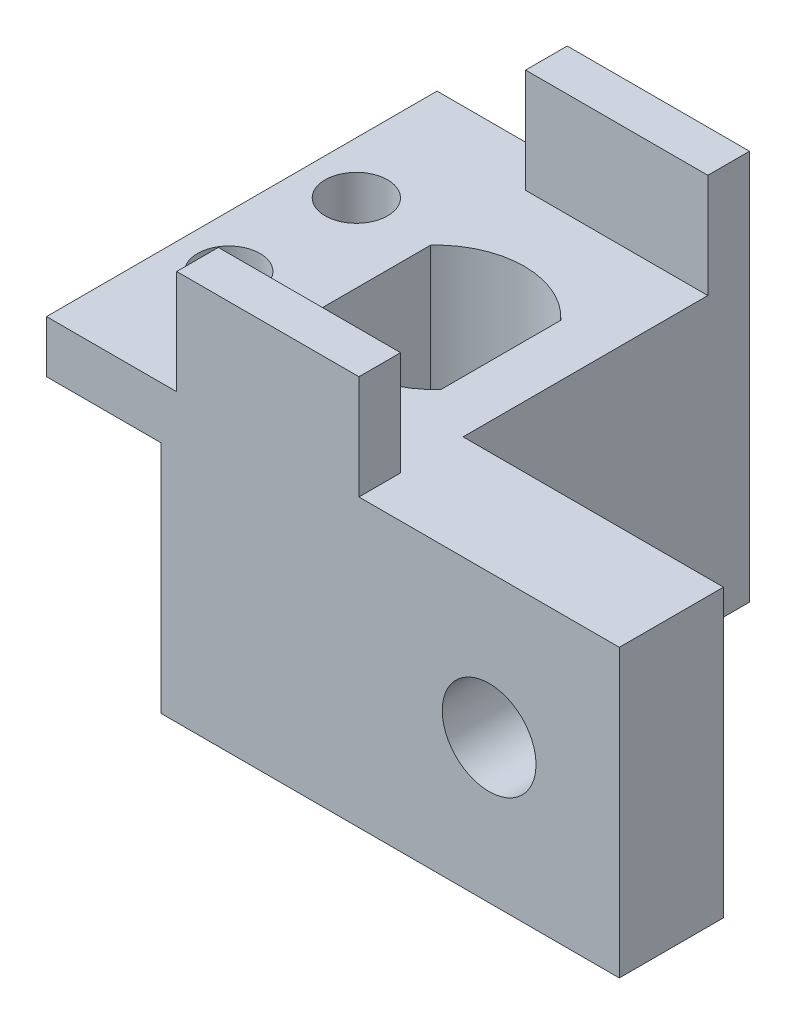
SolidWorks part; units mm, degrees
ref_plane "Front Plane" through (0, 0, 0) normal (0, 0, 1) x (1, 0, 0)
ref_plane "Top Plane" through (0, 0, 0) normal (0, 1, 0) x (1, 0, 0)
ref_plane "Right Plane" through (0, 0, 0) normal (1, 0, 0) x (0, 0, -1)
sketch "Sketch1" plane through (0, 0, 0) normal (0, 1, 0) x (1, 0, 0)
  line L0 (0, 0) -> (12.7, 0)
  line L1 (12.7, 0) -> (12.7, -5.08)
  line L2 (12.7, -5.08) -> (-15.24, -5.08)
  line L3 (-15.24, -5.08) -> (-15.24, 13.97)
  line L4 (-15.24, 13.97) -> (0, 13.97)
  line L5 (0, 13.97) -> (0, 0)
  dimension "D1" = 12.7
  dimension "D2" = 5.08
  dimension "D3" = 27.94
  dimension "D4" = 19.05
extrude "Boss-Extrude1" add sketch "Sketch1" along normal blind 2.54
sketch "Sketch2" plane through (0, 2.54, 0) normal (0, 1, 0) x (1, 0, 0)
  line L0 (12.7, -5.08) -> (-2.54, -5.08) construction
  line L1 (-15.24, -5.08) -> (12.7, -5.08) construction
  line L2 (-2.54, -5.08) -> (-2.54, 4.3815) construction
  line L3 (-2.54, 4.3815) -> (-8.89, 4.3815) construction
  line L4 (-8.89, 1.455) -> (-8.89, 7.308)
  line L5 (-2.54, 1.455) -> (-2.54, 7.308)
  arc A0 (-8.89, 1.455) -> (-2.54, 1.455) centre (-5.715, 4.3815) ccw
  arc A1 (-2.54, 7.308) -> (-8.89, 7.308) centre (-5.715, 4.3815) ccw
  point P10 (-8.89, 4.3815)
  point P13 (-2.54, 4.3815)
  dimension "D1" = 15.24
  dimension "D2" = 9.4615
  dimension "D3" = 6.35
extrude "Cut-Extrude1" cut sketch "Sketch2" against normal blind 23.876 contours L5 A1 L4 A0
sketch "Sketch3" plane through (0, 2.54, 0) normal (0, 1, 0) x (1, 0, 0)
  line L0 (12.7, -5.08) -> (-12.7, -5.08) construction
  line L1 (-15.24, -5.08) -> (12.7, -5.08) construction
  line L2 (-12.7, -5.08) -> (-12.7, 1.27) construction
  line L3 (-2.54, 4.3815) -> (-8.89, 4.3815) construction
  line L4 (-2.54, 1.455) -> (-2.54, 7.308) construction
  line L5 (-8.89, 1.455) -> (-8.89, 7.308) construction
  circle A0 centre (-12.7, 1.27) radius 1.524
  circle A1 centre (-12.7, 7.493) radius 1.524
  dimension "D1" = 25.4
  dimension "D2" = 6.35
extrude "Cut-Extrude2" cut sketch "Sketch3" against normal blind 2.54
sketch "Sketch4" plane through (0, 2.54, 0) normal (0, 1, 0) x (1, 0, 0)
  line L0 (-15.24, 4.445) -> (2.3114, 4.445) construction
  line L1 (0, 13.97) -> (-8.89, 13.97)
  line L2 (0, 13.97) -> (0, 11.938)
  line L3 (0, 11.938) -> (-8.89, 11.938)
  line L4 (-8.89, 13.97) -> (-8.89, 11.938)
  line L5 (-15.24, 13.97) -> (-15.24, -5.08) construction
  line L6 (0, -3.048) -> (-8.89, -3.048)
  line L7 (-8.89, -5.08) -> (-8.89, -3.048)
  line L8 (0, -5.08) -> (-8.89, -5.08)
  line L9 (0, -5.08) -> (0, -3.048)
  dimension "D1" = 8.89
  dimension "D2" = 2.032
extrude "Boss-Extrude2" add sketch "Sketch4" along normal blind 5.08
sketch "Sketch5" plane through (0, 0, 0) normal (0, -1, 0) x (1, 0, 0)
  line L1 (12.7, 5.08) -> (0, 5.08)
  line L2 (12.7, 5.08) -> (12.7, 0)
  line L3 (12.7, 0) -> (0, 0)
  line L4 (0, 5.08) -> (0, 0)
extrude "Boss-Extrude3" add sketch "Sketch5" along normal blind 11.43
sketch "Sketch6" plane through (0, 0, 0) normal (0, 0, -1) x (-1, 0, 0)
  line L0 (-12.7, 2.54) -> (-12.7, -4.445) construction
  line L1 (-12.7, 2.54) -> (-12.7, -11.43) construction
  line L2 (-12.7, -4.445) -> (0, -4.445) construction
  line L3 (0, -11.43) -> (0, 0) construction
  circle A0 centre (-6.35, -4.445) radius 2.286
extrude "Cut-Extrude3" cut sketch "Sketch6" against normal blind 11.43
sketch "Sketch7" plane through (0, 0, 0) normal (0, -1, 0) x (1, 0, 0)
  line L0 (0, -13.97) -> (-15.24, -13.97) construction
  line L1 (0, 5.08) -> (-9.652, 5.08)
  line L2 (0, 5.08) -> (0, -13.97)
  line L3 (0, -13.97) -> (-9.652, -13.97)
  line L4 (-9.652, 5.08) -> (-9.652, -13.97)
  dimension "D1" = 9.652
extrude "Boss-Extrude4" add sketch "Sketch7" along normal blind 11.43
extrude "Cut-Extrude4" cut sketch "Sketch2<3>" against normal blind 25.4
sketch "Sketch2<3>" plane through (0, 2.54, 0) normal (0, 1, 0) x (1, 0, 0) same geometry as "Sketch2"
